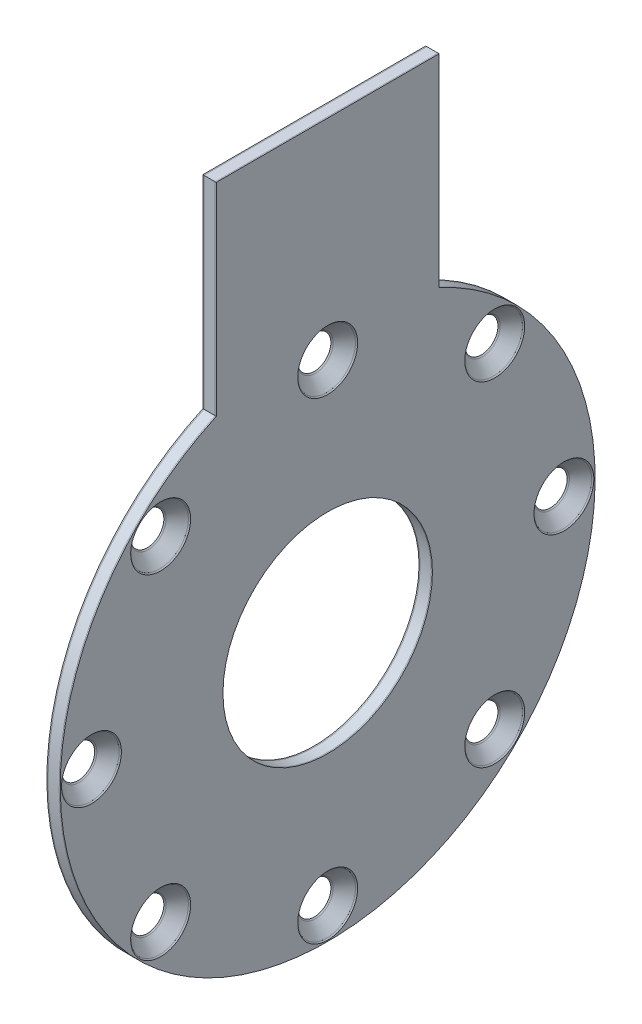
SolidWorks part; units mm, degrees
ref_plane "Front Plane" through (0, 0, 0) normal (0, 0, 1) x (1, 0, 0)
ref_plane "Top Plane" through (0, 0, 0) normal (0, 1, 0) x (1, 0, 0)
ref_plane "Right Plane" through (0, 0, 0) normal (1, 0, 0) x (0, 0, -1)
sketch "Sketch1" plane through (0, 0, 0) normal (1, 0, 0) x (0, 0, -1)
  line L0 (-25, 100) -> (25, 100)
  line L1 (-25, 100) -> (-25, 54.5436)
  line L2 (25, 100) -> (25, 54.5436)
  circle A0 centre (0, 0) radius 60
  circle A1 centre (0, 0) radius 23.5
  point P7 (0, 100)
  dimension "D1" = 120
  dimension "D2" = 47
  dimension "D3" = 40
  dimension "D4" = 50
extrude "Boss-Extrude1" add sketch "Sketch1" along normal blind 0.25 contours A0 L2 L0 L1 | A0 A1 region at (0, 79.0766, 0) region at (0, 58.3029, 0)
sketch "Sketch4" plane through (0, 0, 0) normal (-1, 0, 0) x (0, 0, 1)
  line L3 (25, 54.5436) -> (25, 100)
  line L4 (25, 100) -> (-25, 100)
  line L5 (-25, 100) -> (-25, 54.5436)
  line L6 (25, 54.5436) -> (25, 100)
  line L7 (25, 100) -> (-25, 100)
  line L8 (-25, 100) -> (-25, 54.5436)
  circle A0 centre (0, 0) radius 23.5 construction
  arc A1 (-25, 54.5436) -> (25, 54.5436) centre (0, 0) ccw
  arc A2 (-25, 54.5436) -> (25, 54.5436) centre (0, 0) ccw
  circle A3 centre (0, 0) radius 23.5
  dimension "D1" = 0
extrude "Boss-Extrude4" add sketch "Sketch4" along normal blind 2.5 separate body
sketch "Sketch5" plane through (-2.5, 0, 0) normal (-1, 0, 0) x (0, 0, 1)
  line L3 (25, 54.5436) -> (25, 100)
  line L4 (25, 100) -> (-25, 100)
  line L5 (-25, 100) -> (-25, 54.5436)
  line L6 (25, 54.5436) -> (25, 100)
  line L7 (25, 100) -> (-25, 100)
  line L8 (-25, 100) -> (-25, 54.5436)
  circle A0 centre (0, 0) radius 23.5 construction
  arc A1 (-25, 54.5436) -> (25, 54.5436) centre (0, 0) ccw
  arc A2 (-25, 54.5436) -> (25, 54.5436) centre (0, 0) ccw
  circle A3 centre (0, 0) radius 23.5
  dimension "D1" = 0
extrude "Boss-Extrude5" add sketch "Sketch5" along normal blind 0.25 separate body
sketch "Sketch9" plane through (0.25, 0, 0) normal (1, 0, 0) x (0, 0, -1)
  circle A0 centre (0, 0) radius 53
  point P3 (53, 0)
  point P6 (37.4767, -37.4767)
  point P7 (0, -53)
  point P8 (-37.4767, -37.4767)
  point P9 (-53, 0)
  point P10 (-37.4767, 37.4767)
  point P11 (0, 53)
  point P12 (37.4767, 37.4767)
  dimension "D1" = 106
  dimension "D2" = 8
hole_wizard "CSK for M6 Hex Socket Countersunk Cap Screw2" positions "Sketch9" profile "Sketch10" countersink size "M6" standard "ISO" end condition through all
sketch "Sketch10" plane through (0.25, 37.4767, -37.4767) normal (0, 1, 0) x (0, 0, -1)
  line L0 (0, 0) -> (0, 3)
  line L1 (0, 3) -> (3.3, 3)
  line L2 (3.3, 3) -> (3.3, 3.42)
  line L3 (3.3, 3.42) -> (6.72, 0)
  line L5 (6.72, 0) -> (0, 0)
  line L6 (-3.3, 3.42) -> (-6.72, 0) construction
  line L11 (0, -6.35) -> (0, 107.95) construction
  dimension "Thru Hole Dia." = 6.6
  dimension "Thru Hole Depth" = 3
  dimension "Near C'Sink Dia." = 13.44
  dimension "Near C'Sink Angle" = 90
